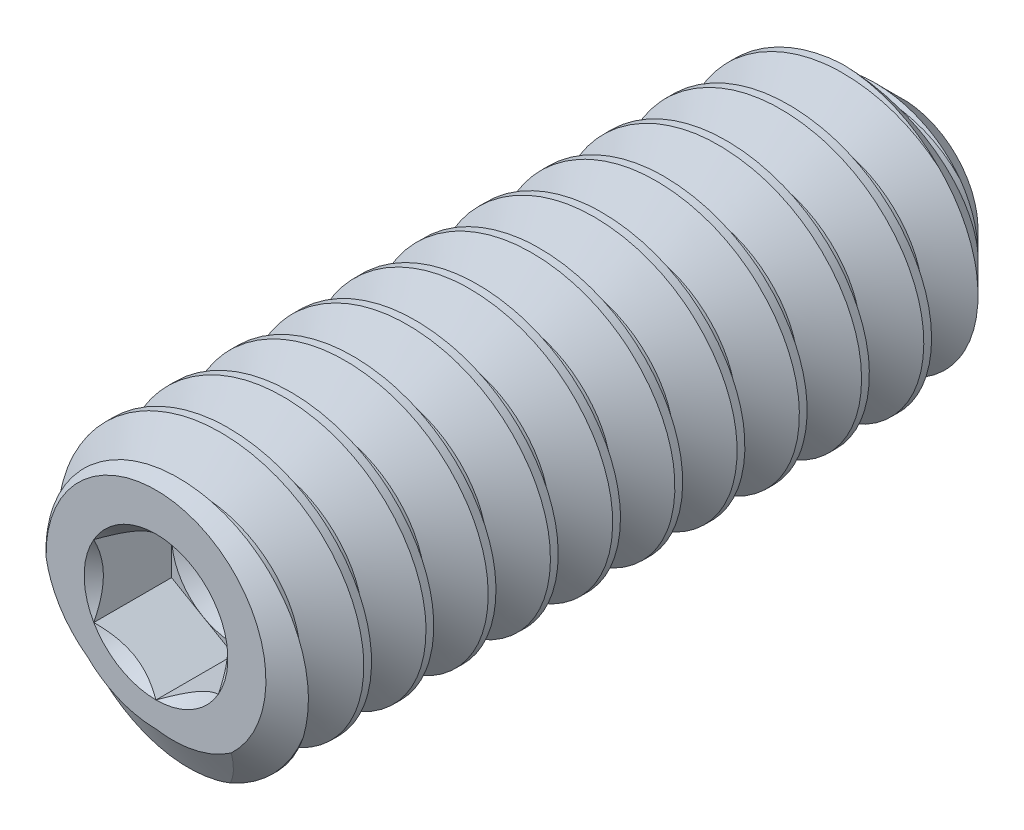
SolidWorks part; units mm, degrees
ref_plane "Front" through (0, 0, 0) normal (0, 0, 1) x (1, 0, 0)
ref_plane "Top" through (0, 0, 0) normal (0, 1, 0) x (1, 0, 0)
ref_plane "Right" through (0, 0, 0) normal (1, 0, 0) x (0, 0, -1)
sketch "Sketch22" plane through (0, 0, 0) normal (1, 0, 0) x (0, 0, -1)
  line L0 (-4.474, 0) -> (-4.474, 1.4021)
  line L1 (-4.474, 1.4021) -> (-4.2285, 1.7526)
  line L2 (-4.2285, 1.7526) -> (4.2588, 1.7526)
  line L3 (4.2588, 1.7526) -> (5.051, 0.9604)
  line L4 (5.051, 0.9604) -> (4.474, 0) construction
  line L5 (4.474, 0) -> (-4.474, 0)
  line L6 (4.474, 0) -> (5.051, 0) construction
  line L7 (5.051, 0) -> (5.051, 0.9604) construction
  line L8 (5.051, -0.9604) -> (4.474, 0) construction
  line L9 (-4.2285, -1.7526) -> (4.2588, -1.7526) construction
  line L10 (5.051, 0.9604) -> (5.051, 0)
  line L11 (5.051, 0) -> (4.474, 0)
  dimension "Dia" = 3.5052
  dimension "Length" = 9.525
  dimension "D3" = 35
  dimension "D5" = 118
  dimension "D6" = 45
  dimension "D7" = 2.8042
revolve "Revolve1" add sketch "Sketch22" angle 360 about L6
ref_plane "Plane1" through (0, 0, -5.051) normal (0, 0, 1) x (1, 0, 0)
sketch "Sketch27" plane through (0, 0, -5.051) normal (0, 0, 1) x (1, 0, 0)
  circle A0 centre (0, 0) radius 1.7526 construction
  circle A1 centre (0, 0) radius 1.7526
curve "Helix/Spiral1" pitch 0.7937 height 10.3188 radius 1.7526 centre (0, 0, -5.051) axis (0, 0, 1) start towards (0, 1, 0)
sketch "Sketch28" plane through (0, 0, 0) normal (1, 0, 0) x (0, 0, -1)
  line L0 (5.051, 1.7526) -> (5.7456, 1.7526)
  line L1 (5.7456, 1.7526) -> (5.4479, 1.237)
  line L2 (5.4479, 1.237) -> (5.3487, 1.237)
  line L3 (5.3487, 1.237) -> (5.051, 1.7526)
  line L4 (5.1999, 1.4948) -> (5.5967, 1.4948) construction
  line L6 (-4.2285, 1.7526) -> (4.2588, 1.7526) construction
  line L7 (5.051, 6.985) -> (5.051, -6.985) construction
  dimension "D1" = 0.0992
  dimension "D2" = 0.3969
  dimension "D3" = 60
sweep "Cut-Sweep2" cut profiles "Sketch28" path "Helix/Spiral1" align with end faces yes
sketch "Sketch23" plane through (0, 0, 4.474) normal (0, 0, 1) x (1, 0, 0)
  line L1 (0, 0.9165) -> (-0.7938, 0.4583)
  line L2 (-0.7938, 0.4583) -> (-0.7938, -0.4583)
  line L3 (-0.7938, -0.4583) -> (0, -0.9165)
  line L4 (0, -0.9165) -> (0.7937, -0.4583)
  line L5 (0.7937, -0.4583) -> (0.7937, 0.4583)
  line L6 (0.7937, 0.4583) -> (0, 0.9165)
  circle A0 centre (0, 0) radius 0.7938 construction
  dimension "Hex" = 1.5875
extrude "Cut-Extrude10" cut sketch "Sketch23" against normal blind 0.9922
sketch "Sketch24" plane through (0, 0, 4.474) normal (0, 0, 1) x (1, 0, 0)
  circle A0 centre (0, 0) radius 0.9165
extrude "Cut-Extrude11" cut sketch "Sketch24" against normal through all draft 45
sketch "Sketch26" plane through (0, 0, 3.4818) normal (0, 0, 1) x (1, 0, 0)
  circle A0 centre (0, 0) radius 0.7938 construction
  circle A1 centre (0, 0) radius 0.7938
extrude "Cut-Extrude12" cut sketch "Sketch26" against normal through all draft 60
sketch "Sketch30" plane through (0, 0, 0) normal (1, 0, 0) x (0, 0, -1)
  line L0 (-4.2285, 1.7526) -> (4.2588, 1.7526) construction
  line L1 (-4.474, 0) -> (-4.474, 1.4021) construction
  line L2 (5.051, 0) -> (5.051, 0.9604) construction
  line L3 (-4.2285, -1.7526) -> (4.2588, -1.7526) construction
  point P0 (-4.474, 1.7526)
  point P1 (5.051, 1.7526)
  point P2 (5.051, -1.7526)
  point P11 (2.2729, -1.7526)
  dimension "D1" = 2.7781
sketch "Sketch31" plane through (0, 0, 0) normal (1, 0, 0) x (0, 0, -1)
  line L2 (4.474, 0) -> (5.051, -0.9604)
  line L3 (5.051, 0.9604) -> (4.474, 0)
equation "\"D7@Sketch22\"=\"Dia@Sketch22\"*.8"
equation "\"D1@Sketch28\" = \"D4@Helix/Spiral1\" * .125"
equation "\"D3@Helix/Spiral1\" = \"Length@Sketch22\" + \"D4@Helix/Spiral1\""
equation "\"D1@Sketch30\" = \"D4@Helix/Spiral1\" * 3.5"
equation "\"hex Depth@Cut-Extrude10\" = \"Hex@Sketch23\" * .625"
equation "\"D2@Sketch28\" = \"D4@Helix/Spiral1\" * .5"
